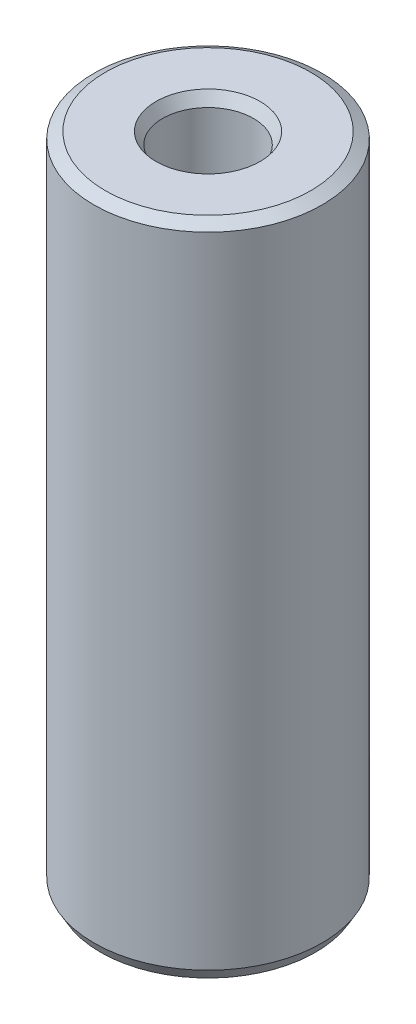
SolidWorks part; units mm, degrees
ref_plane "Front Plane" through (0, 0, 0) normal (0, 0, 1) x (1, 0, 0)
ref_plane "Top Plane" through (0, 0, 0) normal (0, 1, 0) x (1, 0, 0)
ref_plane "Right Plane" through (0, 0, 0) normal (1, 0, 0) x (0, 0, -1)
sketch "Sketch1" plane through (0, 0, 0) normal (0, 1, 0) x (1, 0, 0)
  circle A0 centre (0, 0) radius 7.5
  dimension "SLEEVE_OD" = 15
extrude "Boss-Extrude1" add sketch "Sketch1" along normal blind 43.2007
sketch "Sketch2" plane through (0, 0, 0) normal (0, 1, 0) x (1, 0, 0)
  circle A0 centre (0, 0) radius 2.9896
  dimension "BORE_D" = 5.9792
extrude "Cut-Extrude1" cut sketch "Sketch2" along normal through all
chamfer "Chamfer1" distance 0.4334 angle 60 4 edges at (0, 43.2007, 2.9896) (0, 0, 2.9896) (0, 0, 7.5) (0, 43.2007, 7.5) first distance on face at (0, 43.2007, 2.9896) first distance on face at (0, 0, 2.9896) first distance on face at (0, 43.2007, 7.5)
